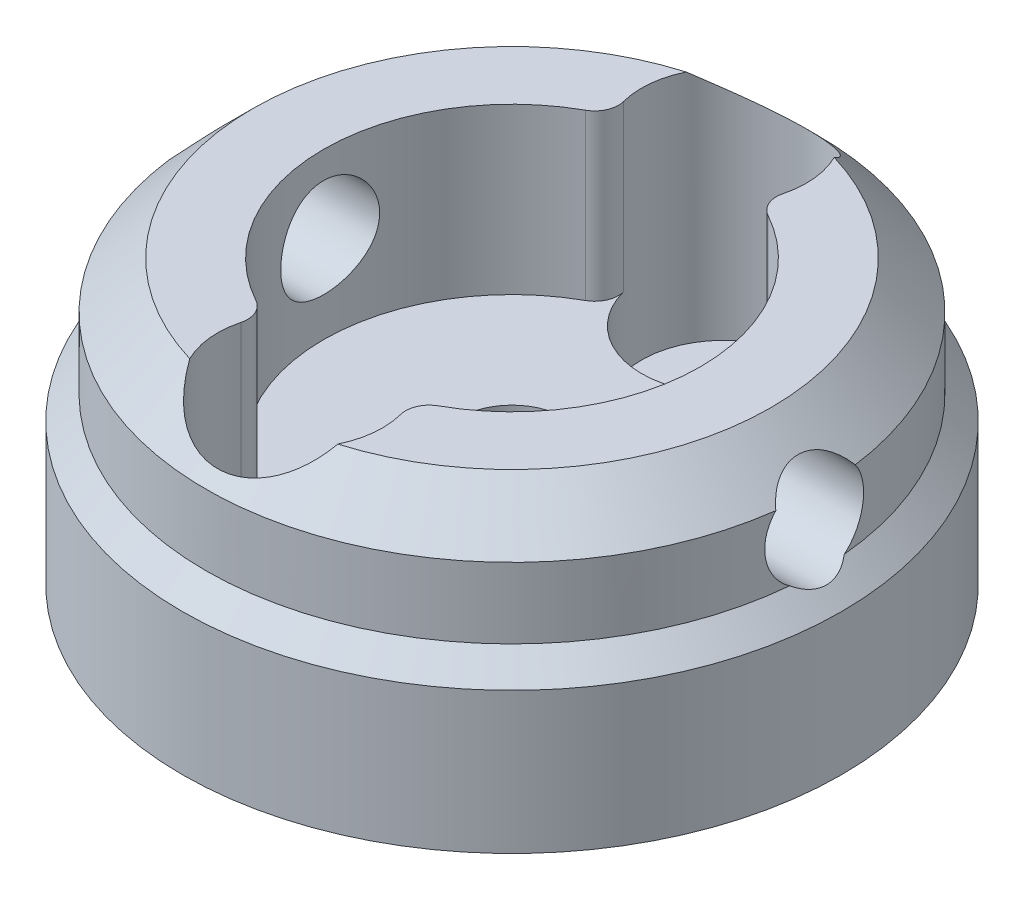
SolidWorks part; units mm, degrees
ref_plane "Front Plane" through (0, 0, 0) normal (0, 0, 1) x (1, 0, 0)
ref_plane "Top Plane" through (0, 0, 0) normal (0, 1, 0) x (1, 0, 0)
ref_plane "Right Plane" through (0, 0, 0) normal (1, 0, 0) x (0, 0, -1)
sketch "Sketch1" plane through (0, 0, 0) normal (0, 1, 0) x (1, 0, 0)
  circle A0 centre (0, 0) radius 14
  circle A1 centre (0, 0) radius 2.25
  dimension "D1" = 28
  dimension "D2" = 4.5
extrude "Boss-Extrude1" add sketch "Sketch1" along normal blind 5
sketch "Sketch2" plane through (0, 5, 0) normal (0, 1, 0) x (1, 0, 0)
  line L0 (0, -1000) -> (0, 49000) construction
  line L1 (-1000, 0) -> (49000, 0) construction
  line L2 (4.2426, 4.2426) -> (0, 0) construction
  circle A0 centre (0, 9) radius 1.5
  circle A1 centre (4.2426, 4.2426) radius 1.5 construction
  dimension "D1" = 3
  dimension "D2" = 3
  dimension "D3" = 9
  dimension "D4" = 6
  dimension "D5" = 45
extrude "Cut-Extrude1" cut sketch "Sketch2" against normal through all
sketch "Sketch4" plane through (0, 5, 0) normal (0, 1, 0) x (1, 0, 0)
  circle A0 centre (0, 9) radius 3.5
  dimension "D1" = 7
extrude "Cut-Extrude2" cut sketch "Sketch4" against normal blind 3
pattern_circular "CirPattern1" count 2 over 360 about axis through (0, 5, 0) along (0, -1, 0) of "Cut-Extrude1", "Cut-Extrude2" reverse direction yes
sketch "Sketch5" plane through (0, 5, 0) normal (0, 1, 0) x (1, 0, 0)
  circle A0 centre (0, 0) radius 8
  circle A1 centre (0, 0) radius 13
  dimension "D1" = 16
  dimension "D2" = 5
extrude "Boss-Extrude2" add sketch "Sketch5" along normal blind 7
sketch "Sketch6" plane through (0, 5, 0) normal (0, 1, 0) x (1, 0, 0)
  circle A2 centre (0, 9) radius 3.5 construction
  circle A3 centre (0, -9) radius 3.5 construction
  circle A6 centre (0, 9) radius 3.5
  circle A7 centre (0, -9) radius 3.5
extrude "Cut-Extrude3" cut sketch "Sketch6" along normal through all
chamfer "Chamfer1" distance 2 angle 45 1 edges at (0, 5, 13)
fillet "Fillet1" radius 1 4 edges at (-3.0999, 8.5, 7.375) (3.0999, 8.5, 7.375) (3.0999, 8.5, -7.375) (-3.0999, 8.5, -7.375)
ref_axis "Axis1" through (0, 12, 12.5) along (0, 0, -1)
ref_plane "Plane1" through (0, 0, 0) normal (1, 0, 0) x (0, 0, -1)
sketch "Sketch8" plane through (0, 0, 0) normal (1, 0, 0) x (0, 0, -1)
  line L0 (15, 5) -> (-15, 5) construction
  circle A0 centre (0, 8.75) radius 2.1
  dimension "D1" = 4.2
  dimension "D2" = 3.75
extrude "Cut-Extrude4" cut sketch "Sketch8" against normal through all and the other way through all
chamfer "Chamfer2" distance 2 angle 45 1 edges at (0, 12, 13)
